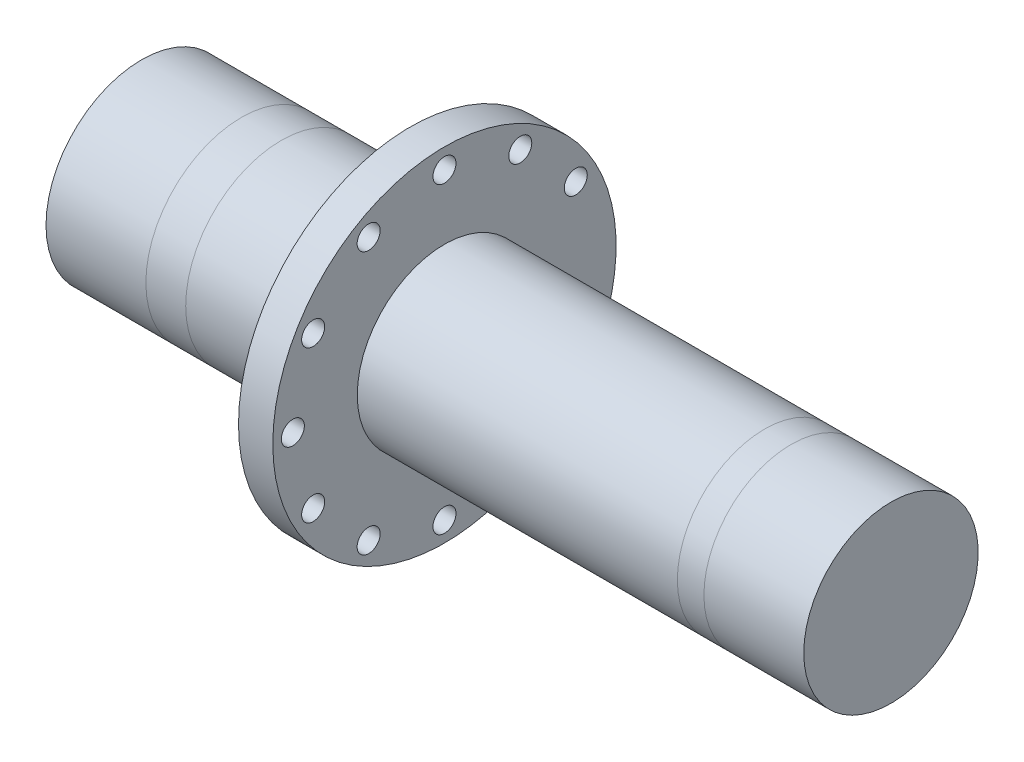
SolidWorks part; units mm, degrees
material "4140 Steel"
ref_plane "Front Plane" through (0, 0, 0) normal (0, 0, 1) x (1, 0, 0)
ref_plane "Top Plane" through (0, 0, 0) normal (0, 1, 0) x (1, 0, 0)
ref_plane "Right Plane" through (0, 0, 0) normal (1, 0, 0) x (0, 0, -1)
sketch "Sketch1" plane through (0, 0, 0) normal (0, 1, 0) x (1, 0, 0)
  line L0 (0, 0) -> (215, 0) construction
  line L1 (0, 0) -> (215, 0)
  line L2 (0, 0) -> (0, 27.432)
  line L3 (0, 27.432) -> (77.05, 27.432)
  line L4 (215, 0) -> (215, 25.019)
  line L5 (76.962, 0) -> (148.082, 0)
  line L6 (77.05, 27.432) -> (77.05, 49.25)
  line L7 (77.05, 49.25) -> (86.8925, 49.25)
  line L9 (148.198, 25.019) -> (215, 25.019)
  line L10 (86.8925, 49.25) -> (86.8925, 25.019)
  line L11 (86.8925, 25.019) -> (148.198, 25.019)
  dimension "D1" = 27.432
  dimension "D2" = 215
  dimension "D3" = 9.8425
  dimension "D4" = 77.05
  dimension "D5" = 25.019
  dimension "D6" = 49.25
revolve "Revolve1" add sketch "Sketch1" angle 360 about L1 region at (104.2412, 0, -13.9609)
sketch "Sketch2" plane through (77.05, 0, 0) normal (-1, 0, 0) x (0, 0, 1)
  line L0 (0, 0) -> (0, 43.5) construction
  circle A15 centre (0, 0) radius 43.5 construction
  circle A16 centre (0, 43.5) radius 3.2639
  circle A17 centre (21.75, 37.6721) radius 3.2639
  circle A18 centre (37.6721, 21.75) radius 3.2639
  circle A19 centre (43.5, 0) radius 3.2639
  circle A20 centre (37.6721, -21.75) radius 3.2639
  circle A21 centre (21.75, -37.6721) radius 3.2639
  circle A22 centre (0, -43.5) radius 3.2639
  circle A23 centre (-21.75, -37.6721) radius 3.2639
  circle A24 centre (-37.6721, -21.75) radius 3.2639
  circle A25 centre (-43.5, 0) radius 3.2639
  circle A26 centre (-37.6721, 21.75) radius 3.2639
  circle A27 centre (-21.75, 37.6721) radius 3.2639
  point P30 (0, 0)
  dimension "D2" = 6.5278
  dimension "D1" = 87
sketch "Sketch3" plane through (0, 0, 0) normal (-1, 0, 0) x (0, 0, 1)
  circle A0 centre (0, 0) radius 19.939
  dimension "D1" = 39.878
ref_plane "Plane1" through (28.65, 0, 0) normal (-1, 0, 0) x (0, 0, 1)
ref_plane "Plane2" through (40.08, 0, 0) normal (-1, 0, 0) x (0, 0, 1)
split line "Split Line1"
ref_plane "Plane3" through (186.35, 0, 0) normal (1, 0, 0) x (0, 0, -1)
ref_plane "Plane4" through (178.73, 0, 0) normal (1, 0, 0) x (0, 0, -1)
split line "Split Line2"
hole_wizard "M6 Clearance Hole1" positions "Sketch6" profile "Sketch7" hole size "M6" standard "ANSI Metric" end condition through all
sketch "Sketch6" plane through (77.05, -169.8128, -45.1356) normal (-1, 0, 0) x (0, 0.9985, 0.0552)
  point P0 (191.6828, 3.1196)
  point P1 (208.4593, -11.8995)
  point P2 (215.4787, -33.2947)
  point P3 (210.86, -55.3332)
  point P4 (195.8408, -72.1097)
  point P5 (174.4456, -79.1291)
  point P6 (152.4071, -74.5104)
  point P7 (135.6306, -59.4912)
  point P8 (128.6112, -38.096)
  point P9 (133.2299, -16.0575)
  point P10 (148.2491, 0.719)
sketch "Sketch7" plane through (77.05, 21.75, -37.6721) normal (0, 1, 0) x (0, 0, 1)
  line L0 (0, 0) -> (0, 137.95)
  line L1 (0, 137.95) -> (3.3, 137.95)
  line L2 (3.3, 137.95) -> (3.3, 0)
  line L3 (3.3, 0) -> (0, 0)
  line L4 (0, -6.35) -> (0, 107.95) construction
  dimension "Thru Hole Dia." = 6.6
  dimension "Thru Hole Depth" = 137.95
